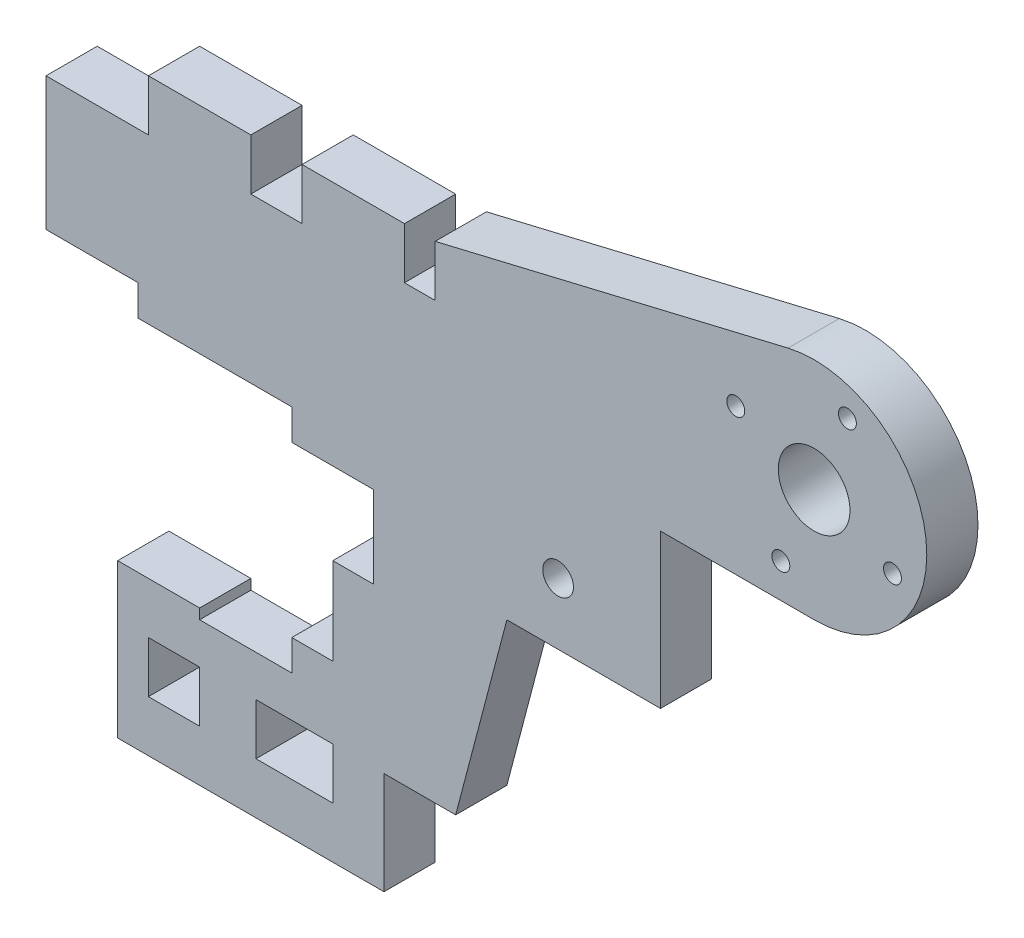
SolidWorks part; units mm, degrees
ref_plane "Plan de face" through (0, 0, 0) normal (0, 0, 1) x (1, 0, 0)
ref_plane "Plan de dessus" through (0, 0, 0) normal (0, 1, 0) x (1, 0, 0)
ref_plane "Plan de droite" through (0, 0, 0) normal (1, 0, 0) x (0, 0, -1)
sketch "Esquisse1" plane through (0, 0, 0) normal (0, 0, 1) x (1, 0, 0)
  line L0 (-8, -10) -> (18, -10)
  line L1 (18, 0) -> (18, -10)
  line L2 (0, 5) -> (0, 4)
  line L3 (5, 42.5) -> (10, 42.5)
  line L4 (56.75, 37.35) -> (63.25, 52.65) construction
  line L5 (20, 42.5) -> (23, 42.5)
  line L6 (-5, 42.5) -> (-5, 47.5)
  line L7 (-5, 47.5) -> (5, 47.5)
  line L8 (5, 42.5) -> (5, 47.5)
  line L9 (18, 0) -> (25, 0)
  line L10 (10, 42.5) -> (10, 47.5)
  line L11 (10, 47.5) -> (20, 47.5)
  line L12 (20, 42.5) -> (20, 47.5)
  line L13 (60, 34) -> (45, 34)
  line L14 (13, 0) -> (5.5, 0)
  line L15 (13, 0) -> (13, -5)
  line L16 (13, -5) -> (5.5, -5)
  line L17 (5.5, 0) -> (5.5, -5)
  line L18 (0, 0) -> (-5, 0)
  line L19 (-6, 29.5) -> (-6, 26.5)
  line L20 (0, 4) -> (9, 4)
  line L21 (60, 45) -> (52.35, 45) construction
  line L22 (-6, 26.5) -> (9, 26.5)
  line L23 (17, 15.5) -> (17, 23.5)
  line L24 (0, 0) -> (0, -5)
  line L25 (0, 0) -> (0, 5)
  line L26 (0, 5) -> (-8, 5)
  line L27 (-8, -10) -> (-8, 5)
  line L28 (-5, 42.5) -> (-15, 42.5)
  line L29 (0, -5) -> (-5, -5)
  line L30 (-6, 29.5) -> (-15, 29.5)
  line L31 (-15, 42.5) -> (-15, 29.5)
  line L32 (17, 23.5) -> (9, 23.5)
  line L33 (52.35, 45) -> (52.35, 48.25) construction
  line L34 (9, 7) -> (13, 7)
  line L35 (9, 23.5) -> (9, 26.5)
  line L36 (17, 15.5) -> (13, 15.5)
  line L37 (67.65, 41.75) -> (52.35, 48.25) construction
  line L38 (30, 19) -> (25, 0)
  line L39 (9, 7) -> (9, 4)
  line L40 (-5, 0) -> (-5, -5)
  line L41 (13, 7) -> (13, 15.5)
  line L42 (57.4528, 55.701) -> (23, 47.5)
  line L43 (45, 19) -> (45, 34)
  line L46 (23, 42.5) -> (23, 47.5)
  line L48 (45, 19) -> (30, 19)
  circle A0 centre (35, 25) radius 1.5
  circle A1 centre (60, 45) radius 3.5
  arc A2 (60, 34) -> (57.4528, 55.701) centre (60, 45) ccw
  circle A3 centre (52.35, 45) radius 0.875 construction
  circle A4 centre (52.35, 48.25) radius 0.875
  circle A5 centre (63.25, 52.65) radius 0.875
  circle A6 centre (67.65, 41.75) radius 0.875
  circle A7 centre (56.75, 37.35) radius 0.875
  point P56 (60, 45)
  dimension "D18" = 7
  dimension "D19" = 3
  dimension "D25" = 3.25
  dimension "D27" = 11
  dimension "D28" = 1.75
  dimension "D24" = 7
  dimension "D3" = 10
  dimension "D4" = 5
  dimension "D5" = 5
  dimension "D6" = 8
  dimension "D7" = 15
  dimension "D8" = 10
  dimension "D9" = 16
  dimension "D10" = 3
  dimension "D11" = 9
  dimension "D12" = 4
  dimension "D13" = 10
  dimension "D14" = 3
  dimension "D15" = 8
  dimension "D16" = 8
  dimension "D17" = 8
  dimension "D20" = 20
  dimension "D21" = 2.5
  dimension "D22" = 17
  dimension "D23" = 25
  dimension "D26" = 7.65
  dimension "D30" = 4
  dimension "D31" = 3
  dimension "D32" = 1
  dimension "D33" = 15
  dimension "D34" = 42.5
  dimension "D35" = 26
  dimension "D36" = 5
  dimension "D37" = 5
  dimension "D38" = 7.5
  dimension "D39" = 5
  dimension "D40" = 104.744
  dimension "D41" = 3
  dimension "D42" = 6
  dimension "D43" = 15
  dimension "D29" = 4
extrude "Boss.-Extru.1" add sketch "Esquisse1" along normal blind 5 contours L5 L12 L11 L10 L3 L8 L7 L6 | L28 L31 L30 | L19 L22 L23 L20 L2 L25 L9 | L27 L25 L26 region at (24.6918, 29.3067, 0)
